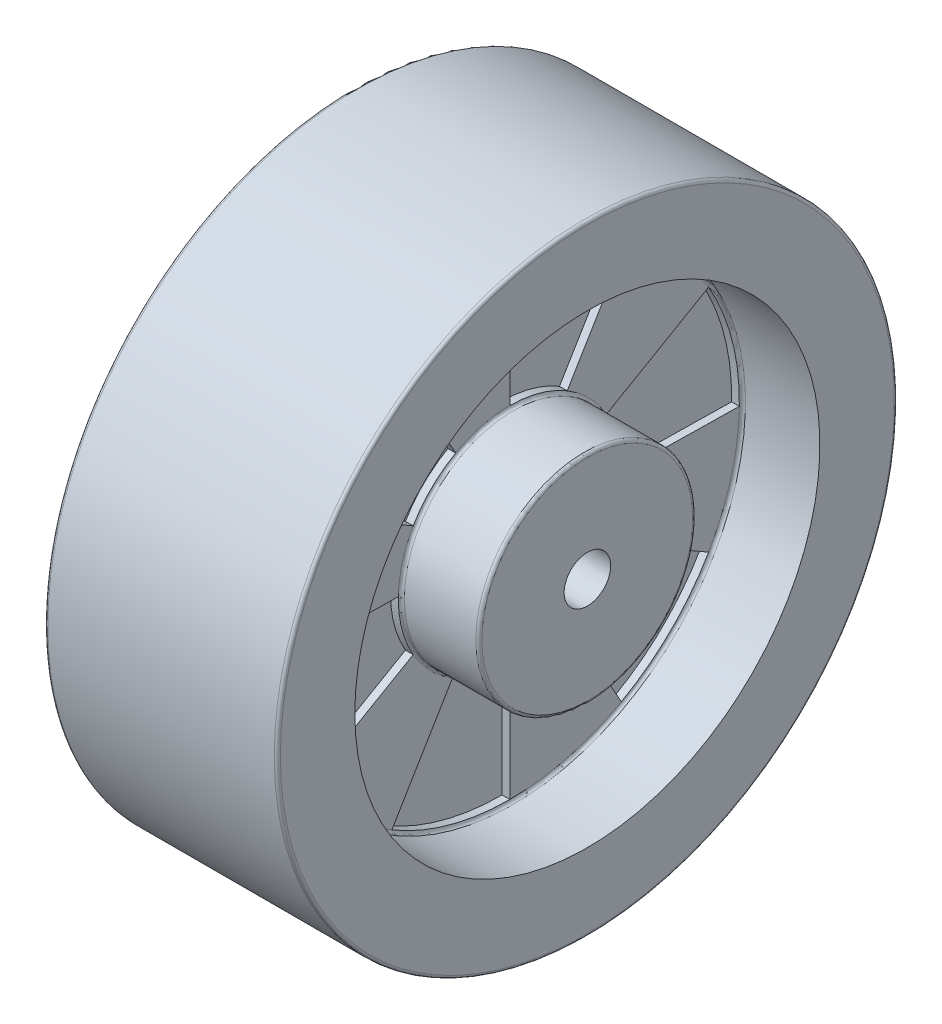
SolidWorks part; units mm, degrees
material "BUTYL"
ref_plane "Front Plane" through (0, 0, 0) normal (0, 0, 1) x (1, 0, 0)
ref_plane "Top Plane" through (0, 0, 0) normal (0, 1, 0) x (1, 0, 0)
ref_plane "Right Plane" through (0, 0, 0) normal (1, 0, 0) x (0, 0, -1)
sketch "Sketch1" plane through (0, 0, 0) normal (0, 0, 1) x (1, 0, 0)
  line L0 (0, 0) -> (56.1842, 0) construction
  line L1 (-38.1, 7.62) -> (38.1, 7.62)
  line L2 (38.1, 7.62) -> (38.1, 35.56)
  line L3 (38.1, 35.56) -> (12.7, 35.56)
  line L4 (12.7, 35.56) -> (12.7, 76.2)
  line L5 (12.7, 76.2) -> (38.1, 76.2)
  line L6 (38.1, 76.2) -> (38.1, 101.6)
  line L7 (38.1, 101.6) -> (-38.1, 101.6)
  line L8 (-38.1, 101.6) -> (-38.1, 76.2)
  line L9 (-38.1, 76.2) -> (-12.7, 76.2)
  line L10 (-12.7, 76.2) -> (-12.7, 35.56)
  line L11 (-12.7, 35.56) -> (-38.1, 35.56)
  line L12 (-38.1, 35.56) -> (-38.1, 7.62)
  line L13 (0, 0) -> (0, 30.585) construction
  point P15 (0, 7.62)
  dimension "D1" = 7.62
  dimension "D2" = 35.56
  dimension "D3" = 76.2
  dimension "D4" = 101.6
  dimension "D5" = 76.2
  dimension "D6" = 25.4
revolve "Revolve1" add sketch "Sketch1" angle 360 about L0
fillet "Fillet1" radius 1 8 edges at (12.7, 0, 76.2) (12.7, 0, 35.56) (38.1, 0, 35.56) (-12.7, 0, 35.56) (-38.1, 0, 35.56) (-12.7, 0, 76.2) (38.1, 0, 101.6) (-38.1, 0, 101.6)
sketch "Sketch2" plane through (12.7, 0, 0) normal (1, 0, 0) x (0, 0, -1)
  line L0 (0, 34.56) -> (0, 76.2)
  line L1 (0, 76.2) -> (0, 34.56)
  line L2 (17.7731, 29.6397) -> (38.6729, 64.4938)
  circle A0 centre (0, 0) radius 76.2 construction
  circle A1 centre (0, 0) radius 75.2 construction
  arc A2 (17.7731, 29.6397) -> (0, 34.56) centre (0, 0) ccw
  arc A3 (38.6729, 64.4938) -> (0, 75.2) centre (0, 0) ccw
  circle M2 centre (0, 0) radius 75.2
  circle M3 centre (0, 0) radius 36.56
extrude "Cut-Extrude1" cut sketch "Sketch2" against normal blind 2.54 contours L2 L0 M3 M2 region at (12.7, 55.3219, -15.3154)
pattern_circular "CirPattern1" count 6 over 360 about axis through (38.1, 0, 0) along (1, 0, 0) of "Cut-Extrude1"
mirror "Mirror1" about plane through (0, 0, 0) normal (1, 0, 0) of "CirPattern1"
